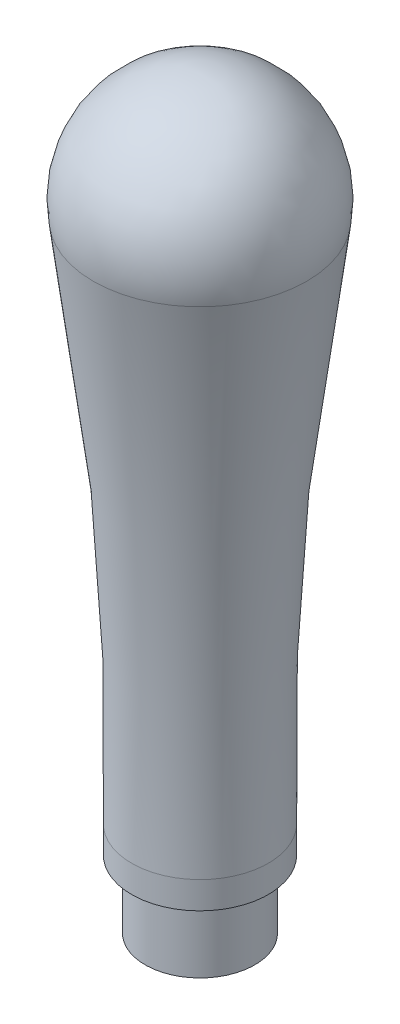
SolidWorks part; units mm, degrees
ref_plane "Front Plane" through (0, 0, 0) normal (0, 0, 1) x (1, 0, 0)
ref_plane "Top Plane" through (0, 0, 0) normal (0, 1, 0) x (1, 0, 0)
ref_plane "Right Plane" through (0, 0, 0) normal (1, 0, 0) x (0, 0, -1)
sketch "Sketch1" plane through (0, 0, 0) normal (0, 0, 1) x (1, 0, 0)
  line L0 (0, 0) -> (4.05, 0)
  line L1 (4.05, 0) -> (4.05, 5)
  line L2 (4.05, 5) -> (5.05, 5)
  line L3 (5.05, 5) -> (5.05, 7)
  line L4 (0, 55) -> (0, 0)
  arc A1 (5.05, 7) -> (7.8844, 45.6447) centre (204.9933, 11.7616) cw
  arc A2 (7.8844, 45.6447) -> (0, 55) centre (0, 47) ccw
  point P5 (5, 7.2511)
  dimension "D6" = 8
  dimension "D7" = 200
  dimension "D1" = 5
  dimension "D2" = 1
  dimension "D3" = 4.05
  dimension "D4" = 2
  dimension "D5" = 50
revolve "Revolve1" add sketch "Sketch1" angle 360 about L4
chamfer "Chamfer1" distance 1 angle 30 1 edges at (-4.05, 5, 0) first distance on face at (-5.05, 5, 0)
